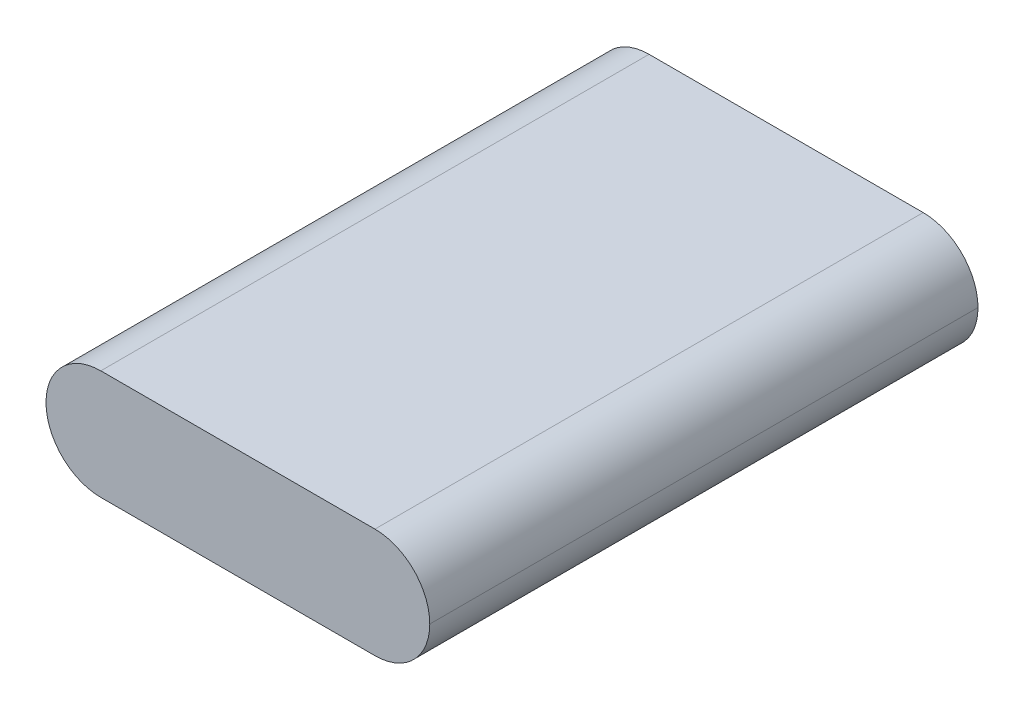
SolidWorks part; units mm, degrees
ref_plane "Front Plane" through (0, 0, 0) normal (0, 0, 1) x (1, 0, 0)
ref_plane "Top Plane" through (0, 0, 0) normal (0, 1, 0) x (1, 0, 0)
ref_plane "Right Plane" through (0, 0, 0) normal (1, 0, 0) x (0, 0, -1)
sketch "Sketch1" plane through (0, 0, 0) normal (0, 1, 0) x (1, 0, 0)
  line L1 (17.5, -25) -> (-17.5, -25)
  line L2 (17.5, -25) -> (17.5, 25)
  line L3 (17.5, 25) -> (-17.5, 25)
  line L4 (-17.5, -25) -> (-17.5, 25)
  line L5 (17.5, -25) -> (-17.5, 25) construction
  line L6 (17.5, 25) -> (-17.5, -25) construction
  point P0 (0, 0)
  dimension "D1" = 35
  dimension "D2" = 50
extrude "Boss-Extrude1" add sketch "Sketch1" along normal blind 10
fillet "Fillet1" radius 5 4 edges at (-17.5, 0, 0) (-17.5, 10, 0) (17.5, 0, 0) (17.5, 10, 0)
